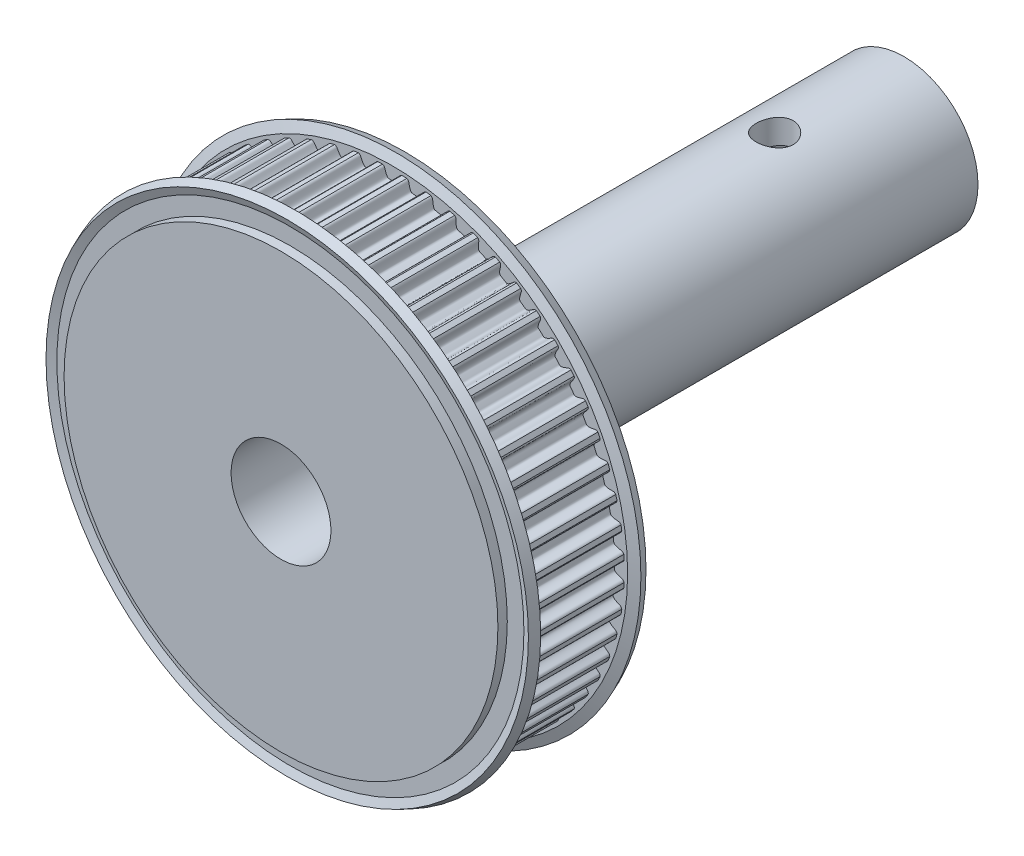
SolidWorks part; units mm, degrees
ref_plane "前视基准面" through (0, 0, 0) normal (0, 0, 1) x (1, 0, 0)
ref_plane "上视基准面" through (0, 0, 0) normal (0, 1, 0) x (1, 0, 0)
ref_plane "右视基准面" through (0, 0, 0) normal (1, 0, 0) x (0, 0, -1)
other "Configuration Table"
ref_axis "基准轴1" through (0, 0, 55) along (0, 0, -1)
sketch "SketchRevolveGearBelt01" plane through (0, 0, 0) normal (1, 0, 0) x (0, 0, -1)
  line L0 (0, 0) -> (1, 0) construction
  line L1 (5.274, 0) -> (5.274, 17.5986)
  line L2 (5.274, 17.5986) -> (4.512, 17.5986)
  line L3 (4.512, 17.5986) -> (4.512, 18.947)
  line L4 (4.512, 18.947) -> (4.7696, 19.569)
  line L5 (4.7696, 19.569) -> (4.0656, 19.8606)
  line L6 (4.0656, 19.8606) -> (3.75, 19.0986)
  line L7 (3.75, 19.0986) -> (3.75, 18.8298)
  line L8 (3.75, 18.8298) -> (-3.75, 18.8298)
  line L9 (-3.75, 18.8298) -> (-3.75, 19.0986)
  line L10 (-3.75, 19.0986) -> (-4.0656, 19.8606)
  line L11 (-4.0656, 19.8606) -> (-4.7696, 19.569)
  line L12 (-4.7696, 19.569) -> (-4.512, 18.947)
  line L13 (-4.512, 18.947) -> (-4.512, 17.5986)
  line L14 (-4.512, 17.5986) -> (-5.274, 17.5986)
  line L15 (-5.274, 17.5986) -> (-5.274, 0)
  line L16 (-5.274, 0) -> (5.274, 0)
  dimension "GearBeltFlange1OutsideLength" = 1.3484
  dimension "GearBeltFlange1X" = 0.2576
  dimension "GearBeltFlange1Y" = 0.622
  dimension "GearBeltFlangeThickness" = 0.762
  dimension "GearBeltFlangeInside" = 0.2688
  dimension "GearBeltOutsideDiameter" = 18.8298
  dimension "GearBeltFlange2X" = 0.2576
revolve "Gates_PowerGrip_GT_2mm, 6mm Belt Width" add sketch "SketchRevolveGearBelt01" angle 360 about L0
sketch "SketchToothGearBelt01" plane through (0, 0, 0) normal (0, 0, 1) x (1, 0, 0)
  arc A0 (18.8246, 0.8608) -> (18.8246, -0.8608) centre (0, 0) cw
  spline S0 degree 3 poles (18.8246, -0.8608) (18.8244, -0.8436) (18.8216, -0.818) (18.813, -0.7848) (18.8042, -0.7607) (18.7932, -0.7375) (18.7799, -0.7155) (18.7646, -0.6948) (18.7474, -0.6758) (18.7284, -0.6584) (18.7079, -0.643) (18.686, -0.6296) (18.6629, -0.6183) (18.6206, -0.6033) (18.5673, -0.5873) (18.5048, -0.5675) (18.4523, -0.5498) (18.4031, -0.5322) (18.357, -0.5145) (18.314, -0.4969) (18.2743, -0.4793) (18.2377, -0.4616) (18.2043, -0.444) (18.174, -0.4264) (18.1469, -0.4087) (18.123, -0.3911) (18.1022, -0.3735) (18.0846, -0.3558) (18.0701, -0.3381) (18.0588, -0.3203) (18.0507, -0.3025) (18.0457, -0.2846) (18.0435, -0.2503) (18.0467, -0.2) (18.0468, -0.1333) (18.0476, -0.0667) (18.0477, 0) (18.0476, 0.0667) (18.0468, 0.1333) (18.0467, 0.2) (18.0435, 0.2503) (18.0457, 0.2846) (18.0507, 0.3025) (18.0588, 0.3203) (18.0701, 0.3381) (18.0846, 0.3558) (18.1022, 0.3735) (18.123, 0.3911) (18.1469, 0.4087) (18.174, 0.4264) (18.2043, 0.444) (18.2377, 0.4616) (18.2743, 0.4793) (18.314, 0.4969) (18.357, 0.5145) (18.4031, 0.5322) (18.4523, 0.5498) (18.5048, 0.5675) (18.5673, 0.5873) (18.6206, 0.6033) (18.6629, 0.6183) (18.686, 0.6296) (18.7079, 0.643) (18.7284, 0.6584) (18.7474, 0.6758) (18.7646, 0.6948) (18.7799, 0.7155) (18.7932, 0.7375) (18.8042, 0.7607) (18.813, 0.7848) (18.8216, 0.818) (18.8244, 0.8436) (18.8246, 0.8608) knots 0 0 0 0 0.019513 0.029269 0.039026 0.048782 0.058538 0.068295 0.078051 0.087808 0.097564 0.10732 0.117077 0.126833 0.158411 0.180602 0.201644 0.221544 0.240311 0.257955 0.274488 0.289925 0.304283 0.317585 0.32986 0.341142 0.351478 0.360929 0.369573 0.377512 0.384878 0.391837 0.398582 0.423956 0.449304 0.474652 0.5 0.525348 0.550696 0.576044 0.601418 0.608163 0.615122 0.622488 0.630427 0.639071 0.648522 0.658858 0.67014 0.682415 0.695717 0.710075 0.725512 0.742045 0.759689 0.778456 0.798356 0.819398 0.841589 0.873167 0.882923 0.89268 0.902436 0.912192 0.921949 0.931705 0.941462 0.951218 0.960974 0.970731 0.980487 1 1 1 1
extrude "ToothExtrudeCutGearBelt01" cut sketch "SketchToothGearBelt01" against normal blind 3.75 and the other way blind 3.75
pattern_circular "Tooth Pattern, 60" count 60 every 6 about axis through (0, 0, 55) along (0, 0, -1) of "ToothExtrudeCutGearBelt01"
sketch "BoreRevolveSketch" plane through (0, 0, 0) normal (1, 0, 0) x (0, 0, -1)
  line L0 (0, 0) -> (1, 0) construction
  line L1 (-5.274, 0) -> (5.274, 0)
  line L2 (5.274, 0) -> (5.274, 5)
  line L3 (5.274, 5) -> (-5.274, 5)
  line L4 (-5.274, 5) -> (-5.274, 0)
  dimension "TaperSide1" = 5
  dimension "TaperSide2" = 5
revolve "BoreRevolveCut" cut sketch "BoreRevolveSketch" angle 360 about L0
sketch "AuxiliarySketchGearBelt01" plane through (0, 0, 0) normal (0, 0, 1) x (1, 0, 0)
  circle A0 centre (0, 0) radius 19.0986 construction
  dimension "PitchDiameter" = 38.1972
sketch "草图5" plane through (0, 0, 5.274) normal (0, 0, 1) x (1, 0, 0)
  circle A0 centre (0, 0) radius 5
extrude "凸台-拉伸1" add sketch "草图5" against normal blind 11
sketch "草图7" plane through (0, 0, -5.274) normal (0, 0, -1) x (-1, 0, 0)
  circle A0 centre (0, 0) radius 6
  dimension "D1" = 12
extrude "凸台-拉伸2" add sketch "草图7" along normal blind 40
sketch "草图8" plane through (0, 0, -45.274) normal (0, 0, -1) x (-1, 0, 0)
  circle A0 centre (0, 0) radius 4.05
  dimension "D1" = 8.1
extrude "切除-拉伸2" cut sketch "草图8" against normal blind 40
sketch "草图9" plane through (0, 0, -5.274) normal (0, 0, -1) x (-1, 0, 0)
  circle A0 centre (0, 0) radius 4.05
extrude "切除-拉伸3" cut sketch "草图9" against normal blind 40
sketch "草图10" plane through (0, 0, 0) normal (0, 1, 0) x (1, 0, 0)
  line L0 (0, 45.274) -> (0, 34.774)
  line L1 (4.05, 45.274) -> (-4.05, 45.274) construction
  line L2 (0, -55) -> (0, 55) construction
  circle A0 centre (0, 34.774) radius 1.5
  dimension "D2" = 3
  dimension "D1" = 10.5
extrude "切除-拉伸4" cut sketch "草图10" against normal through all both and the other way through all contours A0 region at (-1.0307, 0, -33.7433)
